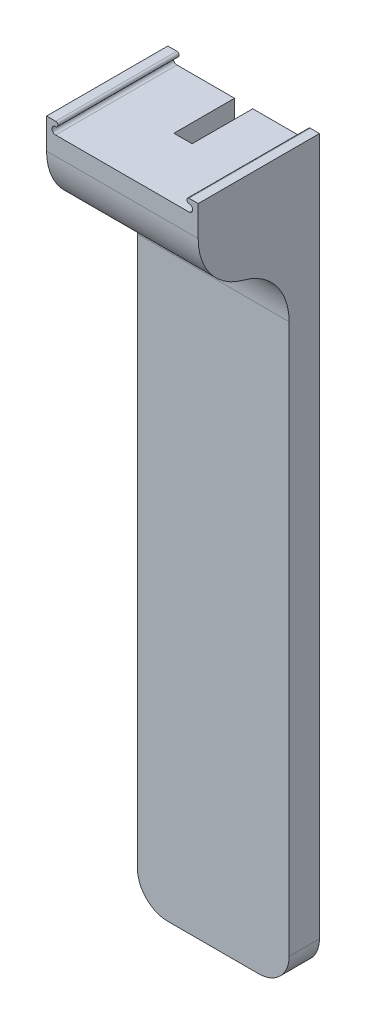
SolidWorks part; units mm, degrees
ref_plane "Přední rovina" through (0, 0, 0) normal (0, 0, 1) x (1, 0, 0)
ref_plane "Horní rovina" through (0, 0, 0) normal (0, 1, 0) x (1, 0, 0)
ref_plane "Pravá rovina" through (0, 0, 0) normal (1, 0, 0) x (0, 0, -1)
sketch "Skica1" plane through (0, 0, 0) normal (0, 0, 1) x (1, 0, 0)
  line L1 (0, 0) -> (25, 0)
  line L2 (0, 0) -> (0, 120)
  line L3 (0, 120) -> (25, 120)
  line L4 (25, 0) -> (25, 120)
  dimension "D1" = 120
  dimension "D2" = 25
extrude "Přidat vysunutím1" add sketch "Skica1" along normal blind 5
sketch "Skica2" plane through (0, 0, 0) normal (0, 0, -1) x (-1, 0, 0)
  line L0 (0, 120) -> (0, 0) construction
  line L1 (-25, 120) -> (0, 120)
  line L2 (-25, 120) -> (-25, 105)
  line L3 (-25, 105) -> (0, 105)
  line L4 (0, 120) -> (0, 105)
  dimension "D1" = 15
extrude "Přidat vysunutím2" add sketch "Skica2" against normal blind 20
fillet "Zaoblit5" radius 5 1 edges at (25, 0, 2.5)
fillet "Zaoblit6" radius 5 1 edges at (0, 0, 2.5)
sketch "Skica3" plane through (0, 0, 20) normal (0, 0, 1) x (1, 0, 0)
  line L0 (1.5, 118.04) -> (23.5, 118.04)
  line L1 (0, 120) -> (25, 120) construction
  line L4 (1.5, 120) -> (23.5, 120)
  line L5 (0, 105) -> (0, 120) construction
  line L6 (25, 120) -> (25, 105) construction
  arc A0 (23.5, 118.04) -> (23.5, 119.24) centre (23.5, 118.64) ccw
  arc A1 (23.5, 119.24) -> (23.5, 120) centre (23.5, 119.62) cw
  arc A2 (1.5, 118.04) -> (1.5, 119.24) centre (1.5, 118.64) cw
  arc A3 (1.5, 119.24) -> (1.5, 120) centre (1.5, 119.62) ccw
  point P18 (0, 0)
  point P19 (0, 0)
  point P20 (0, 0)
  dimension "D1" = 0.6
  dimension "D2" = 0.6
  dimension "D3" = 0.38
  dimension "D4" = 0.38
  dimension "D5" = 1.5
  dimension "D6" = 1.5
  dimension "D7" = 1.96
extrude "Odebrat vysunutím2" cut sketch "Skica3" against normal blind 20
fillet "Zaoblit7" radius 10 1 edges at (12.5, 105, 20)
fillet "Zaoblit8" radius 10 1 edges at (12.5, 105, 5)
sketch "Skica4" plane through (0, 118.04, 0) normal (0, 1, 0) x (1, 0, 0)
  line L0 (1.5, 0) -> (23.5, 0) construction
  line L1 (11, 0) -> (14, 0)
  line L2 (11, 0) -> (11, -10)
  line L3 (11, -10) -> (14, -10)
  line L4 (14, 0) -> (14, -10)
  line L8 (1.5, -20) -> (23.5, -20) construction
  point P6 (12.5, 0)
  point P9 (12.5, -20)
  dimension "D1" = 0
  dimension "D2" = 10
  dimension "D3" = 3
extrude "Odebrat vysunutím3" cut sketch "Skica4" against normal blind 3
